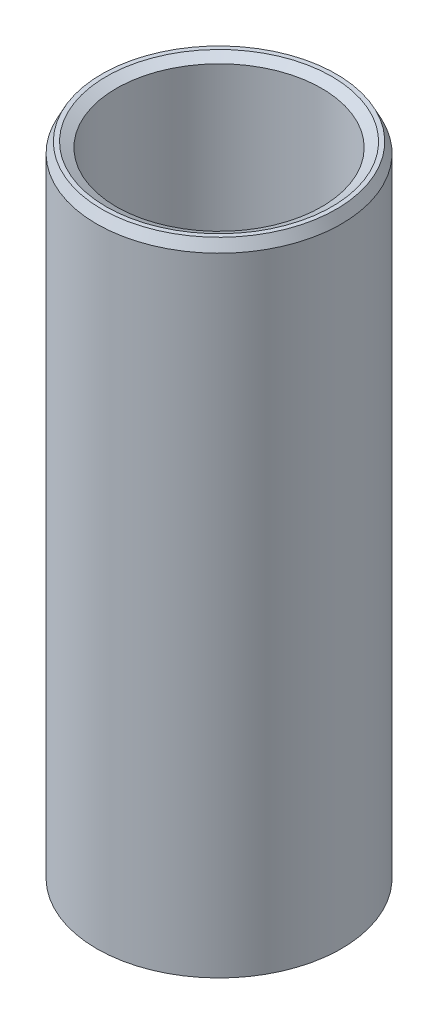
SolidWorks part; units mm, degrees
ref_plane "Front Plane" through (0, 0, 0) normal (0, 0, 1) x (1, 0, 0)
ref_plane "Top Plane" through (0, 0, 0) normal (0, 1, 0) x (1, 0, 0)
ref_plane "Right Plane" through (0, 0, 0) normal (1, 0, 0) x (0, 0, -1)
sketch "Sketch1" plane through (0, 0, 0) normal (0, 1, 0) x (1, 0, 0)
  circle A0 centre (0, 0) radius 22.5
  dimension "SLEEVE_OD" = 45
extrude "Boss-Extrude1" add sketch "Sketch1" along normal blind 118.2566
sketch "Sketch2" plane through (0, 0, 0) normal (0, 1, 0) x (1, 0, 0)
  circle A0 centre (0, 0) radius 18.8775
  dimension "BORE_D" = 37.7549
extrude "Cut-Extrude1" cut sketch "Sketch2" along normal through all
chamfer "Chamfer1" distance 1.8742 angle 26.808 4 edges at (0, 118.2566, 18.8775) (0, 0, 18.8775) (0, 0, 22.5) (0, 118.2566, 22.5) first distance on face at (0, 118.2566, 18.8775) first distance on face at (0, 0, 18.8775) first distance on face at (0, 118.2566, 22.5)
